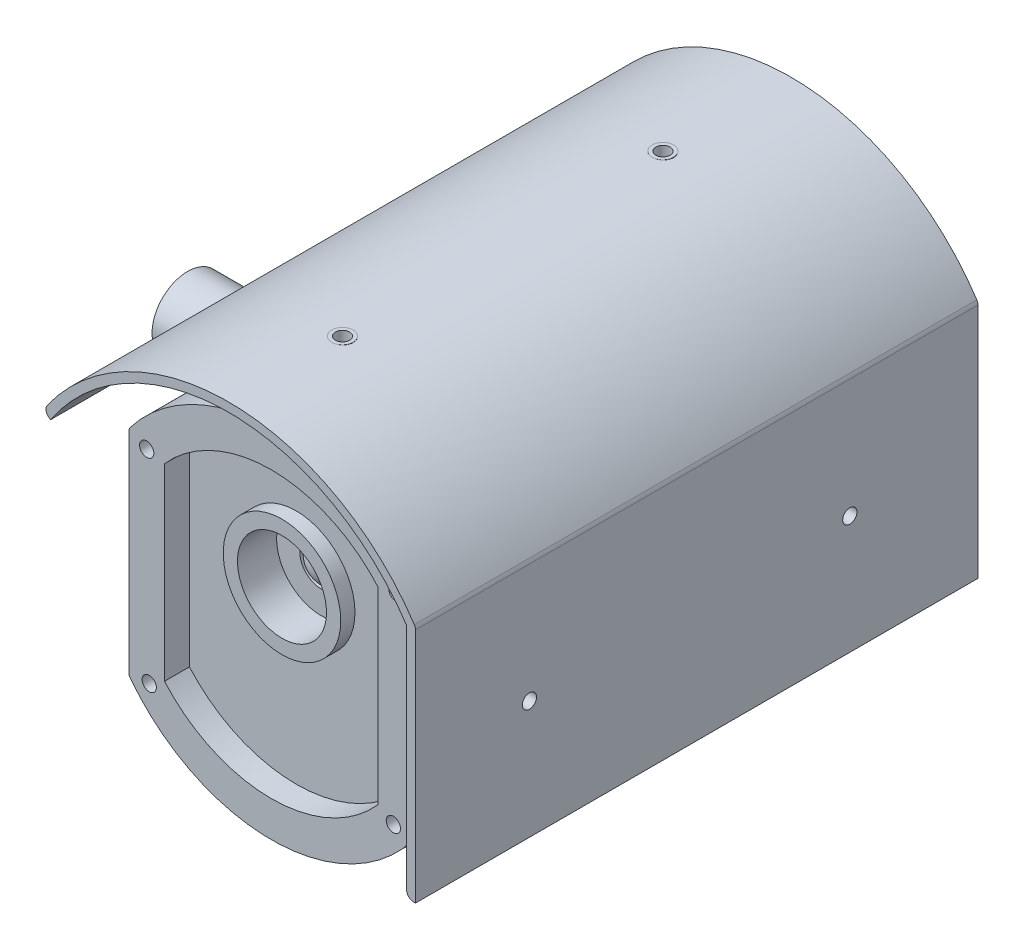
SolidWorks part; units mm, degrees
ref_plane "Front Plane" through (0, 0, 0) normal (0, 0, 1) x (1, 0, 0)
ref_plane "Top Plane" through (0, 0, 0) normal (0, 1, 0) x (1, 0, 0)
ref_plane "Right Plane" through (0, 0, 0) normal (1, 0, 0) x (0, 0, -1)
sketch "Sketch1" plane through (0, 0, 0) normal (0, 0, 1) x (1, 0, 0)
  line L2 (-40, -30) -> (-40, 30)
  line L3 (40, -30) -> (40, 30)
  line L5 (40, 0) -> (-40, 0) construction
  arc A0 (40, 30) -> (-40, 30) centre (0, 0) ccw
  arc A1 (40, -30) -> (-40, -30) centre (0, 0) cw
  point P18 (40, 0)
  point P19 (-40, 0)
  dimension "D1" = 60
  dimension "D2" = 80
extrude "Boss-Extrude1" add sketch "Sketch1" along normal blind 140
sketch "Sketch2" plane through (0, 0, 140) normal (0, 0, 1) x (1, 0, 0)
  line L4 (-30, 26.4575) -> (-30, -26.4575)
  line L5 (30, -26.4575) -> (30, 26.4575)
  line L6 (-30, 26.4575) -> (-30, -26.4575)
  line L7 (30, -26.4575) -> (30, 26.4575)
  arc A4 (30, 26.4575) -> (-30, 26.4575) centre (0, 0) ccw
  arc A5 (-30, -26.4575) -> (30, -26.4575) centre (0, 0) ccw
  arc A6 (30, 26.4575) -> (-30, 26.4575) centre (0, 0) ccw
  arc A7 (-30, -26.4575) -> (30, -26.4575) centre (0, 0) ccw
  dimension "D1" = 10
extrude "Cut-Extrude1" cut sketch "Sketch2" against normal blind 7
sketch "Sketch3" plane through (0, 0, 140) normal (0, 0, 1) x (1, 0, 0)
  line L2 (52.5, -33.1662) -> (52.5, 33.9116)
  line L3 (-50, 33.1662) -> (-52.0833, 34.5482)
  line L4 (-50, 33.1662) -> (-50, -33.1662)
  line L5 (50, -33.1662) -> (50, 33.1662)
  line L6 (52.5, -33.1662) -> (50, -33.1662)
  line L7 (50, -33.1662) -> (50, 33.1662)
  arc A2 (52.5, 33.9116) -> (-52.0833, 34.5482) centre (0, 0) ccw
  arc A4 (50, 33.1662) -> (-50, 33.1662) centre (0, 0) ccw
  arc A5 (-50, -33.1662) -> (50, -33.1662) centre (0, 0) ccw
  arc A6 (50, 33.1662) -> (-50, 33.1662) centre (0, 0) ccw
  dimension "D1" = 10
  dimension "D2" = 2.5
extrude "Boss-Extrude2" add sketch "Sketch3" along normal blind 12 and the other way blind 146 separate body
sketch "Sketch4" plane through (0, 0, 133) normal (0, 0, 1) x (1, 0, 0)
  circle A0 centre (0, 10) radius 12.5
  circle A1 centre (0, 10) radius 16.5
  dimension "D1" = 25
  dimension "D2" = 10
  dimension "D3" = 4
extrude "Boss-Extrude3" add sketch "Sketch4" along normal blind 4
sketch "Sketch5" plane through (0, 0, 133) normal (0, 0, 1) x (1, 0, 0)
  circle A1 centre (0, 10) radius 12.5
  circle A2 centre (0, 10) radius 12.5
  dimension "D1" = 0
extrude "Cut-Extrude2" cut sketch "Sketch5" against normal blind 7
sketch "Sketch6" plane through (0, 0, 126) normal (0, 0, 1) x (1, 0, 0)
  circle A0 centre (0, 10) radius 6
  dimension "D1" = 12
extrude "Cut-Extrude3" cut sketch "Sketch6" against normal blind 1
dome "Dome1" faces to dome 1 distance 3 reverse direction no elliptical dome no face at (6, 10, 125) parameters "D1"=3
sketch "Sketch7" plane through (52.5, 0, 0) normal (1, 0, 0) x (0, 0, -1)
  circle A0 centre (-120, 0) radius 3
  circle A1 centre (-30, 0) radius 3
  dimension "D3" = 6
  dimension "D1" = 90
  dimension "D2" = 30
extrude "Boss-Extrude4" add sketch "Sketch7" against normal up to surface (12.5 mm away) up to face at (40, 0, 70)
sketch "Sketch8" plane through (52.5, 0, 0) normal (1, 0, 0) x (0, 0, -1)
  circle A6 centre (-120, 0) radius 2
  circle A8 centre (-30, 0) radius 2
  dimension "D1" = 4
extrude "Cut-Extrude4" cut sketch "Sketch8" against normal blind 17
ref_plane "Plane1" through (0, 62.5, 0) normal (0, 1, 0) x (-1, 0, 0)
sketch "Sketch9" plane through (0, 62.5, 0) normal (0, 1, 0) x (-1, 0, 0)
  line L0 (-52.5, 120) -> (0, 120) construction
  line L1 (-52.5, 123) -> (-52.5, 117) construction
  circle A0 centre (0, 120) radius 3
  circle A1 centre (0, 30) radius 3
  dimension "D2" = 6
  dimension "D1" = 90
extrude "Boss-Extrude5" add sketch "Sketch9" against normal up to surface (12.5 mm away) up to face at (0, 40, 70)
sketch "Sketch10" plane through (0, 62.5, 0) normal (0, 1, 0) x (1, 0, 0)
  circle A0 centre (0, -30) radius 2
  circle A1 centre (0, -120) radius 2
  arc A2 (0, -123) -> (0, -117) centre (0, -120) ccw construction
  dimension "D1" = 4
extrude "Cut-Extrude5" cut sketch "Sketch10" against normal blind 17
sketch "Sketch11" plane through (0, 0, 0) normal (0, 0, -1) x (-1, 0, 0)
  line L4 (-42, 30.6594) -> (-42, -30.6594)
  line L5 (42, -30.6594) -> (42, 30.6594)
  line L6 (-42, 30.6594) -> (-42, -30.6594)
  line L7 (42, -30.6594) -> (42, 30.6594)
  line L8 (-40, 30) -> (-40, -30)
  line L9 (40, -30) -> (40, 30)
  line L10 (-40, 30) -> (-40, -30)
  line L11 (40, -30) -> (40, 30)
  arc A4 (42, 30.6594) -> (-42, 30.6594) centre (0, 0) ccw
  arc A5 (-42, -30.6594) -> (42, -30.6594) centre (0, 0) ccw
  arc A6 (42, 30.6594) -> (-42, 30.6594) centre (0, 0) ccw
  arc A7 (-42, -30.6594) -> (42, -30.6594) centre (0, 0) ccw
  arc A8 (40, 30) -> (-40, 30) centre (0, 0) ccw
  arc A9 (-40, -30) -> (40, -30) centre (0, 0) ccw
  arc A10 (40, 30) -> (-40, 30) centre (0, 0) ccw
  arc A11 (-40, -30) -> (40, -30) centre (0, 0) ccw
  dimension "D1" = 2
  dimension "D2" = 0
extrude "Boss-Extrude6" add sketch "Sketch11" against normal blind 7
sketch "Sketch12" plane through (0, 0, 0) normal (0, 0, -1) x (-1, 0, 0)
  line L0 (-35, -2.5) -> (35, -2.5)
  line L1 (-35, -6) -> (35, -6)
  line L2 (-35, -12) -> (35, -12)
  line L3 (-35, -8.5) -> (35, -8.5)
  line L4 (-35, 0) -> (35, 0)
  line L5 (-35, 3.5) -> (35, 3.5)
  line L6 (-35, 28.2843) -> (-35, -28.2843)
  line L7 (35, -28.2843) -> (35, 28.2843)
  line L8 (-35, 28.2843) -> (-35, -28.2843)
  line L9 (35, -28.2843) -> (35, 28.2843)
  line L10 (-35, 6) -> (35, 6)
  line L11 (-35, 9.5) -> (35, 9.5)
  line L12 (-35, 12) -> (35, 12)
  line L13 (-35, 15.5) -> (35, 15.5)
  line L14 (-35, 18) -> (35, 18)
  line L15 (-35, 21.5) -> (35, 21.5)
  line L16 (-35, 24) -> (35, 24)
  line L17 (-35, 27.5) -> (35, 27.5)
  line L18 (-33.541, 30) -> (33.541, 30)
  line L19 (-30.0458, 33.5) -> (30.0458, 33.5)
  line L20 (-27, 36) -> (27, 36)
  line L21 (-21.5581, 39.5) -> (21.5581, 39.5)
  line L22 (-16.1555, 42) -> (16.1555, 42)
  line L23 (-35, -18) -> (35, -18)
  line L24 (-35, -14.5) -> (35, -14.5)
  line L25 (-35, -24) -> (35, -24)
  line L26 (-35, -20.5) -> (35, -20.5)
  line L27 (-33.541, -30) -> (33.541, -30)
  line L28 (-35, -26.5) -> (35, -26.5)
  line L29 (-35, 45.5) -> (35, 45.5) [skipped]
  line L30 (-27, -36) -> (27, -36)
  line L31 (-31.1247, -32.5) -> (31.1247, -32.5)
  line L32 (-16.1555, -42) -> (16.1555, -42)
  line L33 (-23.297, -38.5) -> (23.297, -38.5)
  arc A7 (35, 28.2843) -> (-35, 28.2843) centre (0, 0) ccw
  arc A8 (-35, -28.2843) -> (35, -28.2843) centre (0, 0) ccw
  arc A9 (35, 28.2843) -> (-35, 28.2843) centre (0, 0) ccw
  arc A10 (-35, -28.2843) -> (35, -28.2843) centre (0, 0) ccw
  dimension "D2" = 3.5
  dimension "D4" = 2.5
  dimension "D5" = 3.5
  dimension "D1" = 7
  dimension "D3" = 8
  dimension "D6" = 7
extrude "Cut-Extrude6" cut sketch "Sketch12" against normal blind 5 contours L22 A9 | L20 A9 L21 | L18 A9 L19 | L17 L8 L16 L9 | L15 L8 L14 L9 | L13 L8 L12 L9 | L11 L8 L10 L9 | L4 L9 L5 L8 | L1 L9 L0 L8 | L2 L9 L3 L8 | L24 L8 L23 L9 | L26 L8 L25 L9 | L8 A10 L27 L9 L28 | L31 A10 L30 | L33 A10 L32 region at (0, -4.25, 0) region at (0, 1.75, 0) region at (0, -10.25, 0) region at (0, 7.75, 0) region at (0, -16.25, 0) region at (0, 13.75, 0) region at (0, -22.25, 0) region at (0, 19.75, 0) region at (0, -28.238, 0) region at (0, 25.75, 0) region at (0, -34.2088, 0) region at (0, 31.718, 0) region at (0, -40.1467, 0) region at (0, 37.6852, 0) region at (0, 43.2035, 0)
sketch "Sketch13" plane through (-40, 0, 0) normal (-1, 0, 0) x (0, 0, 1)
  line L0 (73.5, -30) -> (73.5, 0) construction
  line L1 (140, -30) -> (7, -30) construction
  circle A0 centre (73.5, 0) radius 10
  dimension "D1" = 20
extrude "Boss-Extrude7" add sketch "Sketch13" along normal blind 50
sketch "Sketch14" plane through (-40, 0, 0) normal (-1, 0, 0) x (0, 0, 1)
  circle A0 centre (73.5, 0) radius 10 construction
  circle A1 centre (73.5, 0) radius 10
  circle A2 centre (73.5, 0) radius 15
  dimension "D1" = 5
extrude "Boss-Extrude8" add sketch "Sketch14" along normal blind 20
fillet "Fillet1" radius 2 24 edges at (40, -3, 30) (40, -3, 120) (50, -3, 30) (50, -3, 120) (-0.684, 49.9953, 27.079) (0.6858, 59.9961, 27.0794) (-0.684, 49.9953, 117.079) (0.6858, 59.9961, 117.0794) (-40, 30, 73.5) (-40, -30, 73.5) (40, -30, 73.5) (40, 30, 73.5) (52.5, 33.9116, 73) (50, -33.1662, 73) (-52.0833, 34.5482, 73) (-40, 15, 73.5) (42, 30.6594, 3.5) (42, -30.6594, 3.5) (0, -52, 0) (42, 0, 0) (0, 52, 0) (-42, 30.6594, 3.5) (-42, -30.6594, 3.5) (-42, 0, 0)
sketch "Sketch15" plane through (0, 0, 140) normal (0, 0, 1) x (1, 0, 0)
  circle A0 centre (35, 27.5) radius 2
  circle A1 centre (-35, 27.5) radius 2
  circle A3 centre (34.2812, -29.1513) radius 2
  arc A4 (33.541, -30) -> (35, -28.2843) centre (0, 0) ccw construction
  circle A5 centre (-34.2812, -29.1513) radius 2
  arc A6 (-35, -28.2843) -> (-33.541, -30) centre (0, 0) ccw construction
  dimension "D1" = 4
extrude "Cut-Extrude7" cut sketch "Sketch15" against normal blind 5
